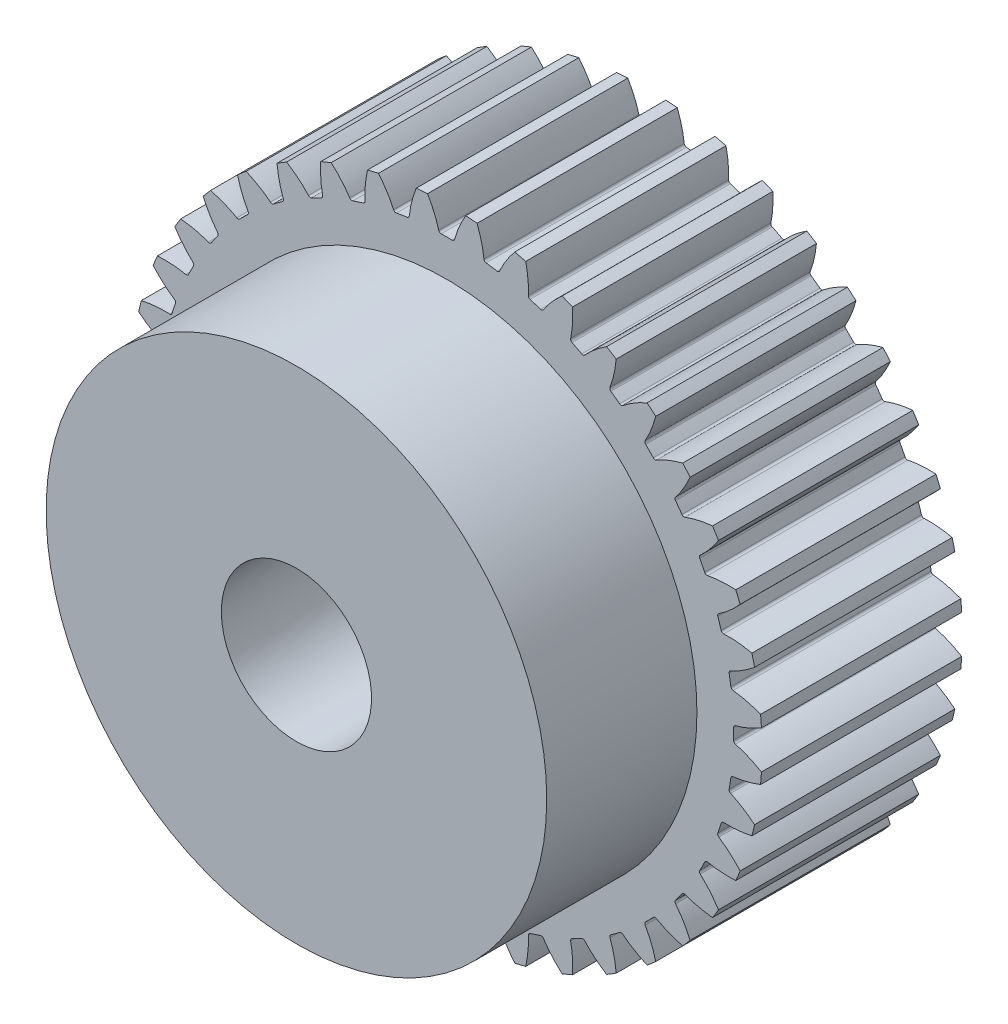
SolidWorks part; units mm, degrees
ref_plane "Front Plane" through (0, 0, 0) normal (0, 0, 1) x (1, 0, 0)
ref_plane "Top Plane" through (0, 0, 0) normal (0, 1, 0) x (1, 0, 0)
ref_plane "Right Plane" through (0, 0, 0) normal (1, 0, 0) x (0, 0, -1)
sketch "Sketch1" plane through (0, 0, 0) normal (0, 0, 1) x (1, 0, 0)
  line L0 (0, 30) -> (0, -30) construction
  line L1 (0, -30) -> (8.8305, -30) construction
  line L2 (0, -30) -> (9.6418, -26.4907) construction
  line L3 (0, 0) -> (9.6418, -26.4907)
  line L4 (0, 0) -> (-28.1284, 0) construction
  line L5 (-28.1284, 1.875) -> (-28.1284, -1.875) construction
  line L6 (-28.1284, 1.875) -> (0, 0) construction
  line L7 (0, 0) -> (-28.1284, -1.875) construction
  line L8 (0, 0) -> (-20.6686, 19.1711) construction
  line L9 (0, 0) -> (-17.9401, 21.7456) construction
  line L10 (0, 0) -> (-14.894, 23.9351) construction
  line L11 (0, 0) -> (-11.5842, 25.7007) construction
  line L12 (0, 0) -> (-8.0692, 27.0113) construction
  line L13 (0, 0) -> (-4.4113, 27.8435) construction
  line L14 (-4.4113, 27.8435) -> (-0.7075, 28.4303) construction
  line L15 (-8.0692, 27.0113) -> (-0.883, 29.158) construction
  line L16 (-11.5842, 25.7007) -> (-1.3279, 30.3236) construction
  line L17 (-14.894, 23.9351) -> (-2.1584, 31.86) construction
  line L18 (-17.9401, 21.7456) -> (-3.4769, 33.6778) construction
  line L19 (-20.6686, 19.1711) -> (-5.3675, 35.6673) construction
  circle A0 centre (0, 0) radius 28.1908 construction
  arc A1 (1.1779, 29.9769) -> (-1.1779, 29.9769) centre (0, 0) ccw construction
  circle A2 centre (0, 30) radius 1.1781 construction
  circle A3 centre (0, 0) radius 28.6595
  circle A4 centre (0, 0) radius 31.5
  circle A5 centre (0, 0) radius 7.5
  circle A6 centre (0, 0) radius 25
  spline S0 degree 3 poles (-5.3675, 35.6673) (-4.1503, 34.5369) (-2.6529, 32.8286) (-1.3674, 30.4884) (-0.9147, 29.3232) (-0.6834, 28.4341) (-0.6286, 27.5171) (-0.6989, 26.269) (-1.1981, 23.646) (-2.0942, 21.5586) (-2.9023, 20.1072) knots 0 0 0 0 0.285711 0.385711 0.45714 0.5 0.54286 0.614289 0.714289 1 1 1 1
  spline S1 degree 3 poles (5.3675, 35.6673) (4.1503, 34.5369) (2.6529, 32.8286) (1.3674, 30.4884) (0.9147, 29.3232) (0.6834, 28.4341) (0.6286, 27.5171) (0.6989, 26.269) (1.1981, 23.646) (2.0942, 21.5586) (2.9023, 20.1072) knots 0 0 0 0 0.285711 0.385711 0.45714 0.5 0.54286 0.614289 0.714289 1 1 1 1
  point P3 (-2.9023, 20.1072)
  point P4 (0, 0)
  point P16 (-28.1284, 0)
  point P27 (-1.7192, 22.5838)
  point P28 (-1.0272, 24.72)
  point P29 (-0.7123, 26.438)
  point P30 (-0.6494, 27.684)
  dimension "D4" = 2.3562
  dimension "D17" = 63
  dimension "D18" = 57.3191
  dimension "D19" = 15
  dimension "D20" = 50
  dimension "D1" = 20
  dimension "D2" = 60
  dimension "D3" = 90
  dimension "D5" = 3.75
  dimension "D6" = 7.63
  dimension "D7" = 7.63
  dimension "D8" = 7.63
  dimension "D9" = 7.63
  dimension "D10" = 7.63
  dimension "D11" = 3.75
  dimension "D12" = 7.5
  dimension "D13" = 11.25
  dimension "D14" = 15
  dimension "D15" = 18.75
  dimension "D16" = 22.5
extrude "Boss-Extrude1" add sketch "Sketch1" along normal blind 20 contours A4
extrude "Cut-Extrude2" cut sketch "Sketch1<5>" along normal through all contours S1 A4 S0 A3 region at (0, 30.2907, 0)
sketch "Sketch1<5>" plane through (0, 0, 0) normal (0, 0, 1) x (1, 0, 0) same geometry as "Sketch1"
fillet "Fillet1" radius 0.25 2 edges at (0.7485, 28.6498, 10) (-0.7485, 28.6498, 10)
pattern_circular "CirPattern1" count 40 over 360 about axis through (0, 0, 20) along (0, 0, -1) of "Cut-Extrude2", "Fillet1" reverse direction yes
extrude "Boss-Extrude2" add sketch "Sketch1<8>" along normal blind 35 contours A6
sketch "Sketch1<8>" plane through (0, 0, 0) normal (0, 0, 1) x (1, 0, 0) same geometry as "Sketch1"
sketch "Sketch2" plane through (0, 0, 0) normal (0, 0, -1) x (-1, 0, 0)
  circle A0 centre (0, 0) radius 7.5
  dimension "D1" = 15
extrude "Cut-Extrude4" cut sketch "Sketch2" against normal through all
equation "\"boss\"= 50mm"
equation "\"bore\"= 15mm"
equation "\"pcd\"= 60mm"
equation "\"d\"= 63mm"
equation "\"e\"= 7.63"
equation "\"x\"= 3.75"
equation "\"y\"= 1"
equation "\"z\"= 1"
equation "\"D2@Sketch1\"=\"pcd\""
equation "\"D4@Sketch1\"=3/4*pi"
equation "\"D6@Sketch1\"=\"e\""
equation "\"D7@Sketch1\"=\"e\""
equation "\"D8@Sketch1\"=\"e\""
equation "\"D9@Sketch1\"=\"e\""
equation "\"D10@Sketch1\"=\"e\""
equation "\"D12@Sketch1\"=\"x\"*2"
equation "\"D13@Sketch1\"=\"x\"*3"
equation "\"D14@Sketch1\"=\"x\"*4"
equation "\"D15@Sketch1\"=\"x\"*5"
equation "\"D16@Sketch1\"=\"x\"*6"
equation "\"D17@Sketch1\"=\"d\""
equation "\"D19@Sketch1\"=\"bore\""
equation "\"D20@Sketch1\"=\"boss\""
equation "\"D1@Sketch2\"=\"bore\""
